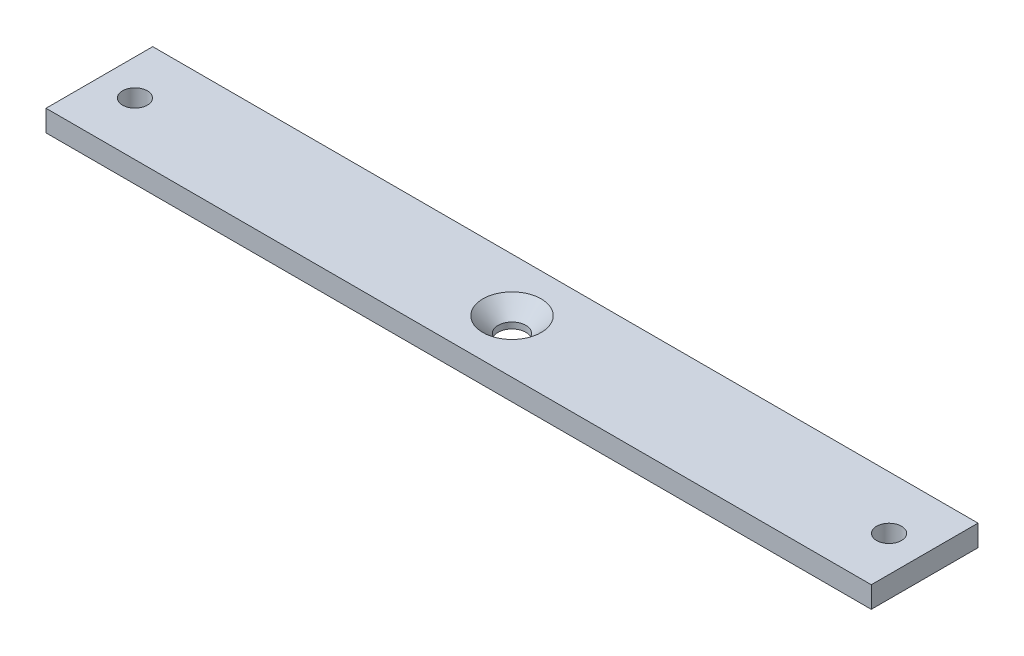
SolidWorks part; units mm, degrees
ref_plane "Спереди" through (0, 0, 0) normal (0, 0, 1) x (1, 0, 0)
ref_plane "Сверху" through (0, 0, 0) normal (0, 1, 0) x (1, 0, 0)
ref_plane "Справа" through (0, 0, 0) normal (1, 0, 0) x (0, 0, -1)
sketch "Эскиз1" plane through (0, 0, 0) normal (0, 1, 0) x (1, 0, 0)
  line L0 (-53, 0) -> (53, 0)
  line L1 (-58, -7.5) -> (58, -7.5)
  line L2 (-58, -7.5) -> (-58, 7.5)
  line L3 (-58, 7.5) -> (58, 7.5)
  line L4 (58, -7.5) -> (58, 7.5)
  line L5 (-58, -7.5) -> (58, 7.5) construction
  line L6 (-58, 7.5) -> (58, -7.5) construction
  circle A0 centre (53, 0) radius 1.75
  circle A1 centre (-53, 0) radius 1.75
  circle A2 centre (0, 0) radius 1.75
  point P0 (0, 0)
  point P9 (0, 0)
extrude "Бобышка-Вытянуть1" add sketch "Эскиз1" along normal blind 1.5 and the other way blind 1.5 contours L1 L4 L3 L2 A1 A0 region at (-56.8303, 0, 0)
hole_wizard "Зенковка для  винта с плоской головкой M3.51" positions "Трехмерный эскиз1" profile "Эскиз2" countersink size "M3.5" standard "Ansi Metric" end condition through all
sketch3d "Трехмерный эскиз1"
  line L0 (0, -1.5, 0) -> (0, 1.5, 0) construction
  point P0 (0, 1.5, 0)
sketch "Эскиз2" plane through (0, 1.5, 0) normal (1, 0, 0) x (0, 0, 1)
  line L0 (0, 0) -> (0, 3)
  line L1 (0, 3) -> (1.95, 3)
  line L2 (1.95, 3) -> (1.95, 2.15)
  line L3 (1.95, 2.15) -> (4.1, 0)
  line L5 (4.1, 0) -> (0, 0)
  line L6 (-1.95, 2.15) -> (-4.1, 0) construction
  line L11 (0, -6.35) -> (0, 107.95) construction
  dimension "Диаметр сквозного отверстия" = 3.9
  dimension "Глубина сквозного отверстия" = 3
  dimension "Диаметр передней зенковки" = 8.2
  dimension "Угол передней зенковки" = 90
